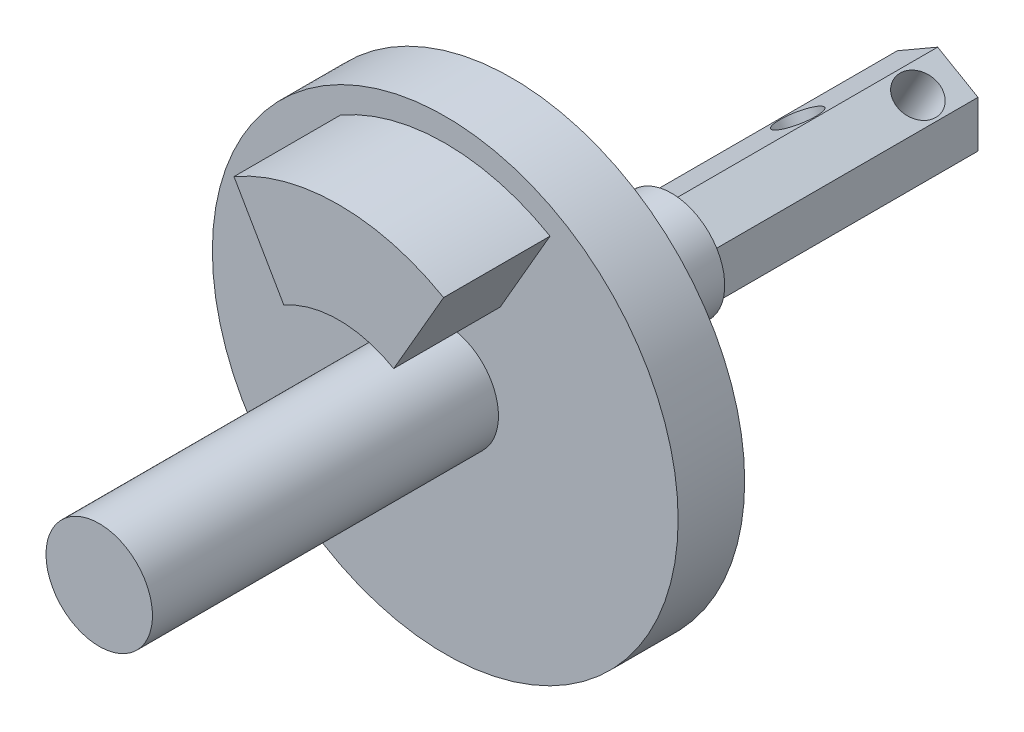
SolidWorks part; units mm, degrees
ref_plane "Front Plane" through (0, 0, 0) normal (0, 0, 1) x (1, 0, 0)
ref_plane "Top Plane" through (0, 0, 0) normal (0, 1, 0) x (1, 0, 0)
ref_plane "Right Plane" through (0, 0, 0) normal (1, 0, 0) x (0, 0, -1)
sketch "Sketch1" plane through (0, 0, 0) normal (0, 0, 1) x (1, 0, 0)
  circle A0 centre (0, 0) radius 17.5
  dimension "D1" = 35
extrude "Boss-Extrude1" add sketch "Sketch1" along normal mid plane 5
sketch "Sketch2" plane through (0, 0, 2.5) normal (0, 0, 1) x (1, 0, 0)
  line L3 (0, 0) -> (0, 11) construction
  line L4 (7.875, 13.6399) -> (4.125, 7.1447)
  line L5 (-4.125, 7.1447) -> (-7.875, 13.6399)
  arc A1 (4.125, 7.1447) -> (-4.125, 7.1447) centre (0, 0) ccw
  arc A6 (-7.875, 13.6399) -> (7.875, 13.6399) centre (0, 0) cw
  circle A7 centre (0, 0) radius 17.5 construction
  dimension "D2" = 7.5
  dimension "D3" = 1.75
  dimension "D1" = 30
extrude "Boss-Extrude2" add sketch "Sketch2" along normal blind 8
sketch "Sketch3" plane through (0, 0, 2.5) normal (0, 0, 1) x (1, 0, 0)
  circle A0 centre (0, 0) radius 4
extrude "Boss-Extrude3" add sketch "Sketch3" along normal blind 26
sketch "Sketch7" plane through (0, 0, -2.5) normal (0, 0, -1) x (-1, 0, 0)
  circle A0 centre (0, 0) radius 4
extrude "Boss-Extrude4" add sketch "Sketch7" along normal blind 12
sketch "Sketch9" plane through (0, 0, -14.5) normal (0, 0, -1) x (-1, 0, 0)
  line L11 (0, 3.5) -> (-3.0311, 1.75)
  line L12 (-3.0311, 1.75) -> (-3.0311, -1.75)
  line L13 (-3.0311, -1.75) -> (0, -3.5)
  line L14 (0, -3.5) -> (3.0311, -1.75)
  line L15 (3.0311, -1.75) -> (3.0311, 1.75)
  line L16 (3.0311, 1.75) -> (0, 3.5)
  point P5 (0, 0)
  point P6 (0, 0)
  point P8 (0, 0)
  point P11 (0, 0)
  point P13 (0, 0)
  point P15 (0, 0)
extrude "Boss-Extrude5" add sketch "Sketch9" along normal blind 20
sketch "Sketch10" plane through (-1.5155, -2.625, 0) normal (-0.5, -0.866, 0) x (0.866, -0.5, 0)
  line L0 (0, -34.5) -> (0, -31.5) construction
  line L1 (1.75, -34.5) -> (-1.75, -34.5) construction
  circle A0 centre (0, -31.5) radius 1.55
  point P7 (0, -31.1402)
extrude "Cut-Extrude1" cut sketch "Sketch10" against normal blind 6.1
sketch "Sketch11" plane through (1.5155, -2.625, 0) normal (-0.5, 0.866, 0) x (0, 0, 1)
  line L0 (-34.5, 0) -> (-25.5, 0) construction
  line L3 (-34.5, -1.75) -> (-34.5, 1.75) construction
  circle A1 centre (-25.5, 0) radius 1.55
extrude "Cut-Extrude4" cut sketch "Sketch11" along normal blind 6.1
